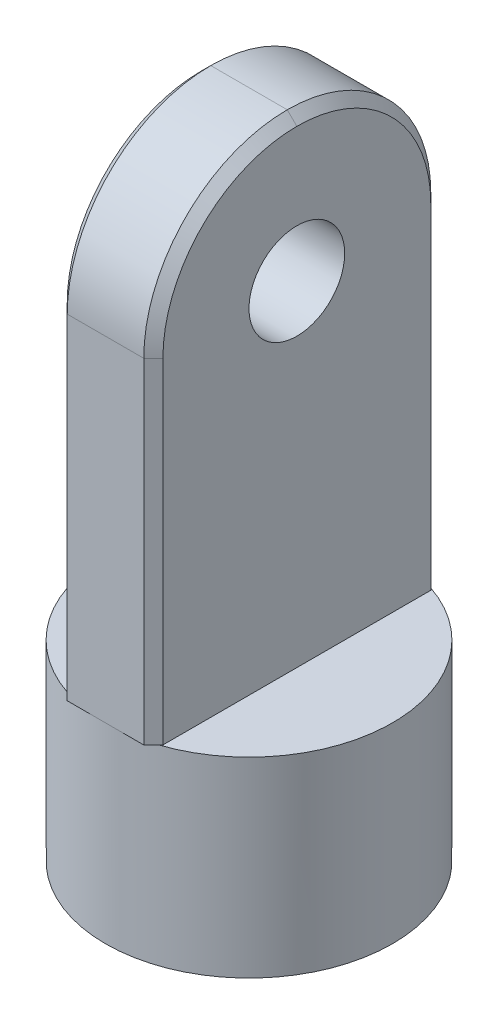
SolidWorks part; units mm, degrees
ref_plane "Front Plane" through (0, 0, 0) normal (0, 0, 1) x (1, 0, 0)
ref_plane "Top Plane" through (0, 0, 0) normal (0, 1, 0) x (1, 0, 0)
ref_plane "Right Plane" through (0, 0, 0) normal (1, 0, 0) x (0, 0, -1)
sketch "Sketch1" plane through (0, 0, 0) normal (0, 1, 0) x (1, 0, 0)
  circle A0 centre (0, 0) radius 7.5
  dimension "D1" = 15
extrude "Boss-Extrude1" add sketch "Sketch1" along normal blind 10
sketch "Sketch2" plane through (0, 0, 0) normal (0, -1, 0) x (1, 0, 0)
  circle A0 centre (0, 0) radius 6.25
  dimension "D1" = 12.5
extrude "Cut-Extrude2" cut sketch "Sketch2" against normal blind 7.5
sketch "Sketch3" plane through (0, 10, 0) normal (0, 1, 0) x (1, 0, 0)
  line L1 (-2.5, -7.5) -> (2.5, -7.5)
  line L2 (-2.5, -7.5) -> (-2.5, 7.5)
  line L3 (-2.5, 7.5) -> (2.5, 7.5)
  line L4 (2.5, -7.5) -> (2.5, 7.5)
  line L5 (-2.5, -7.5) -> (2.5, 7.5) construction
  line L6 (-2.5, 7.5) -> (2.5, -7.5) construction
  point P0 (0, 0)
  dimension "D1" = 5
  dimension "D2" = 15
extrude "Boss-Extrude2" add sketch "Sketch3" along normal blind 25
sketch "Sketch4" plane through (2.5, 0, 0) normal (1, 0, 0) x (0, 0, -1)
  line L0 (-7.5, 35) -> (7.5, 35) construction
  line L1 (-7.5, 35) -> (-7.5, 10) construction
  circle A0 centre (0, 27.5) radius 2.5
  point P4 (0, 0)
  dimension "D1" = 5
  dimension "D2" = 7.5
  dimension "D3" = 7.5
extrude "Cut-Extrude3" cut sketch "Sketch4" against normal blind 5
fillet "Fillet1" radius 7.5 2 edges at (0, 35, -7.5) (0, 35, 7.5)
chamfer "Chamfer1" distance 0.5 angle 45 8 edges at (2.5, 18.75, -7.5) (2.5, 32.8033, -5.3033) (2.5, 32.8033, 5.3033) (2.5, 18.75, 7.5) (-2.5, 18.75, -7.5) (-2.5, 32.8033, -5.3033) (-2.5, 32.8033, 5.3033) (-2.5, 18.75, 7.5)
